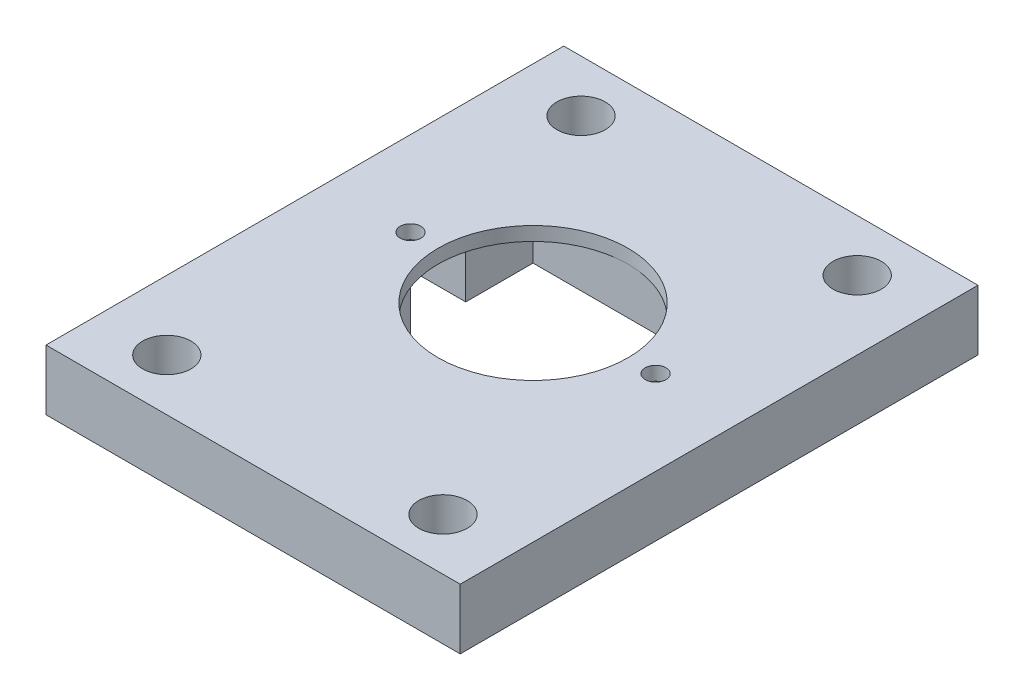
SolidWorks part; units mm, degrees
material "ABS"
ref_plane "Front Plane" through (0, 0, 0) normal (0, 0, 1) x (1, 0, 0)
ref_plane "Top Plane" through (0, 0, 0) normal (0, 1, 0) x (1, 0, 0)
ref_plane "Right Plane" through (0, 0, 0) normal (1, 0, 0) x (0, 0, -1)
sketch "Sketch1" plane through (0, 0, 0) normal (0, 1, 0) x (1, 0, 0)
  line L1 (15.24, -19.05) -> (-15.24, -19.05)
  line L2 (15.24, -19.05) -> (15.24, 19.05)
  line L3 (15.24, 19.05) -> (-15.24, 19.05)
  line L4 (-15.24, -19.05) -> (-15.24, 19.05)
  line L5 (15.24, -19.05) -> (-15.24, 19.05) construction
  line L6 (15.24, 19.05) -> (-15.24, -19.05) construction
  line L10 (-15.24, 0) -> (49984.76, 0) construction
  line L11 (0, 18.415) -> (0, -49981.585) construction
  circle A0 centre (-10.16, 15.24) radius 1.778
  circle A1 centre (10.16, 15.24) radius 1.778
  circle A2 centre (-10.16, -15.24) radius 1.778
  circle A3 centre (10.16, -15.24) radius 1.778
  point P0 (0, 0)
  point P8 (-15.24, 0)
  point P9 (15.24, 0)
  point P12 (0, 19.05)
  point P13 (0, -19.05)
  dimension "D3" = 3.556
  dimension "D4" = 30.48
  dimension "D5" = 20.32
  dimension "D1" = 38.1
  dimension "D2" = 30.48
extrude "Boss-Extrude1" add sketch "Sketch1" along normal blind 4.445
sketch "Sketch2" plane through (0, 0, 0) normal (0, -1, 0) x (1, 0, 0)
  line L0 (0, 15.24) -> (0, -49984.76) construction
  line L1 (-10.16, 15.24) -> (10.16, 15.24) construction
  line L2 (-10.16, 15.24) -> (-10.16, -15.24) construction
  line L3 (-10.16, -15.24) -> (10.16, -15.24) construction
  line L4 (10.16, 15.24) -> (10.16, -15.24) construction
  circle A0 centre (-10.16, -15.24) radius 1.778 construction
  circle A1 centre (10.16, -15.24) radius 1.778 construction
  circle A2 centre (10.16, 15.24) radius 1.778 construction
  circle A3 centre (-10.16, 15.24) radius 1.778 construction
  circle A4 centre (-10.16, -15.24) radius 1.778
  circle A5 centre (10.16, -15.24) radius 1.778
  circle A6 centre (10.16, 15.24) radius 1.778
  circle A7 centre (-10.16, 15.24) radius 1.778
  circle A8 centre (0, -1.5494) radius 6.985
  circle A9 centre (-9.017, -1.5494) radius 0.762
  circle A10 centre (9.017, -1.5494) radius 0.762
  point P15 (0, -15.24)
  point P19 (0, 15.24)
  dimension "D1" = 13.97
  dimension "D2" = 13.6906
  dimension "D3" = 1.524
  dimension "D4" = 18.034
extrude "Cut-Extrude1" cut sketch "Sketch2" against normal through all
sketch "Sketch3" plane through (0, 0, 0) normal (0, -1, 0) x (1, 0, 0)
  line L0 (-6.985, -8.5344) -> (6.985, -8.5344)
  line L1 (-6.985, -8.5344) -> (-6.985, 5.4356)
  line L2 (6.985, -8.5344) -> (6.985, 5.4356)
  line L3 (-6.985, 5.4356) -> (6.985, 5.4356)
  line L4 (-6.985, -8.5344) -> (6.985, 5.4356) construction
  line L5 (6.985, -8.5344) -> (-6.985, 5.4356) construction
  line L6 (0, -8.5344) -> (0, 49991.4656) construction
  line L8 (-11.049, 0.4826) -> (-6.985, 0.4826)
  line L9 (-11.049, 0.4826) -> (-11.049, -3.5814)
  line L10 (-11.049, -3.5814) -> (-6.985, -3.5814)
  line L11 (-6.985, 0.4826) -> (-6.985, -3.5814)
  line L15 (11.049, -3.5814) -> (6.985, -3.5814)
  line L16 (6.985, 0.4826) -> (6.985, -3.5814)
  line L17 (11.049, 0.4826) -> (6.985, 0.4826)
  line L18 (11.049, 0.4826) -> (11.049, -3.5814)
  circle A0 centre (0, -1.5494) radius 6.985 construction
  circle A4 centre (-9.017, -1.5494) radius 0.762 construction
  circle A5 centre (-9.017, -1.5494) radius 0.762
  point P3 (0, 5.4356)
  point P4 (6.985, -1.5494)
  point P13 (0, -8.5344)
  circle M13 centre (0, -1.5494) radius 6.985
  dimension "D1" = 2.032
  dimension "D2" = 2.032
  dimension "D3" = 2.032
extrude "Cut-Extrude2" cut sketch "Sketch3" against normal blind 3.429 contours L1 L0 M13 | L3 L1 M13 | L3 L2 M13 | L2 | L9 L10 L1 L8 | L0 L2 M13 region at (-5.4248, 0, -6.9742) region at (5.4248, 0, -6.9742) region at (-9.017, 0, -3.5239) region at (-5.4248, 0, 3.8754) region at (9.017, 0, -1.5494) region at (5.4248, 0, 3.8754)
